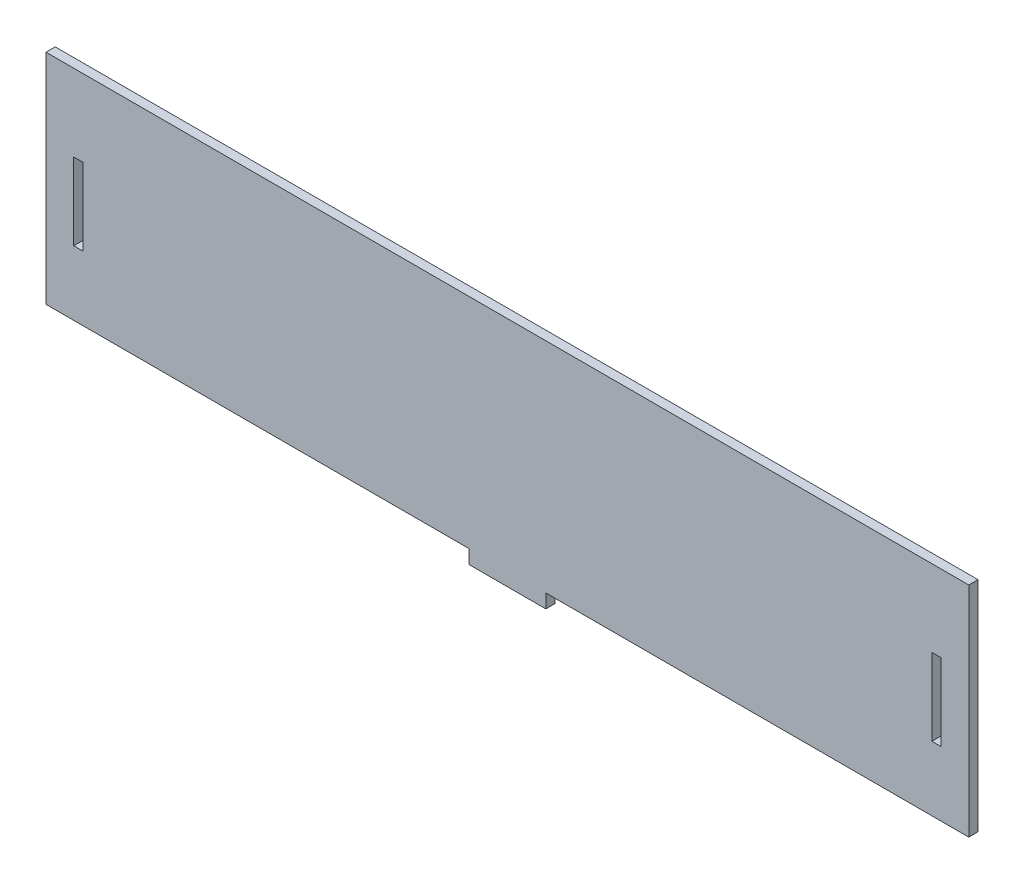
SolidWorks part; units mm, degrees
material "Maple"
ref_plane "Front Plane" through (0, 0, 0) normal (0, 0, 1) x (1, 0, 0)
ref_plane "Top Plane" through (0, 0, 0) normal (0, 1, 0) x (1, 0, 0)
ref_plane "Right Plane" through (0, 0, 0) normal (1, 0, 0) x (0, 0, -1)
sketch "Sketch1" plane through (0, 0, 0) normal (0, 0, 1) x (1, 0, 0)
  line L0 (300, 0) -> (300, -90) construction
  line L1 (0, 0) -> (600, 0)
  line L2 (0, 0) -> (0, -142)
  line L3 (0, -142) -> (275, -142)
  line L4 (600, 0) -> (600, -142)
  line L6 (325, -142) -> (600, -142)
  line L8 (275, -142) -> (275, -151)
  line L9 (275, -151) -> (325, -151)
  line L10 (325, -142) -> (325, -151)
  line L11 (582, -100) -> (576, -100)
  line L12 (18, -50) -> (24, -50)
  line L13 (18, -50) -> (18, -100)
  line L14 (18, -100) -> (24, -100)
  line L15 (24, -50) -> (24, -100)
  line L16 (18, -50) -> (24, -100) construction
  line L17 (18, -100) -> (24, -50) construction
  line L18 (576, -50) -> (576, -100)
  line L19 (582, -50) -> (576, -50)
  line L20 (582, -50) -> (582, -100)
  point P10 (21, -75)
  dimension "D1" = 600
  dimension "142" = 142
  dimension "D3" = 50
  dimension "D4" = 6
  dimension "D5" = 50
  dimension "D6" = 18
  dimension "D7" = 275
  dimension "D8" = 275
  dimension "D9" = 50
extrude "Boss-Extrude1" add sketch "Sketch1" along normal blind 6
